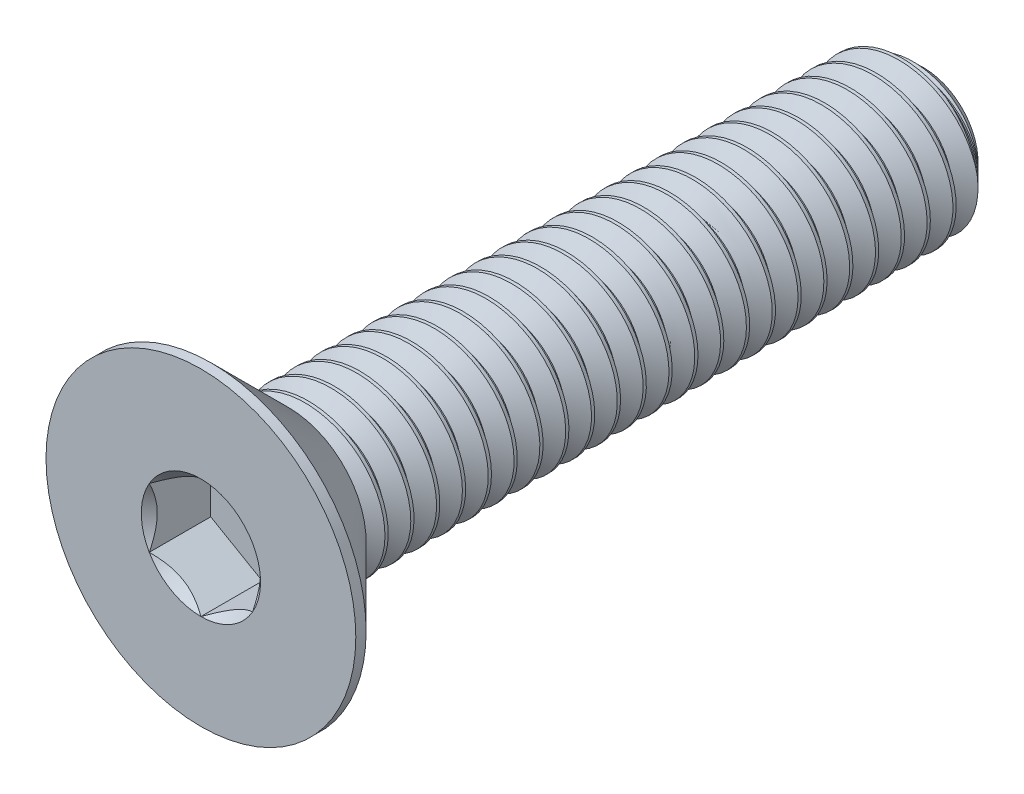
SolidWorks part; units mm, degrees
ref_plane "Front" through (0, 0, 0) normal (0, 0, 1) x (1, 0, 0)
ref_plane "Top" through (0, 0, 0) normal (0, 1, 0) x (1, 0, 0)
ref_plane "Right" through (0, 0, 0) normal (1, 0, 0) x (0, 0, -1)
sketch "Sketch1" plane through (0, 0, 0) normal (1, 0, 0) x (0, 0, -1)
  line L0 (-7, 3) -> (-6.8, 3) construction
  line L1 (-6.8, 3) -> (-5.3, 1.5) construction
  line L2 (-7, 1.5) -> (7, 1.5) construction
  line L3 (7, 1.5) -> (7, 0) construction
  line L4 (7, 0) -> (-7, 0) construction
  line L5 (-7, 0) -> (-7, 3) construction
  line L6 (-7, 3) -> (-7, -3) construction
  line L7 (7, 1.5) -> (7, -1.5) construction
  line L8 (-7, -3) -> (-6.8, -3) construction
  line L9 (-6.8, -3) -> (-5.3, -1.5) construction
  line L11 (-7, 1.5) -> (-7, 0) construction
  line L12 (-5.3, 1.5) -> (-5.3, 0) construction
  line L13 (6.9687, 1.5541) -> (7.2187, 1.1211) construction
  line L14 (7.2187, 1.1211) -> (7.4687, 1.5541) construction
  line L15 (7.4687, 1.5541) -> (6.9687, 1.5541) construction
  line L16 (7.2187, 1.5541) -> (7.2187, 1.5) construction
  line L17 (7.2187, 1.5) -> (7.2187, 1.1752) construction
  line L18 (7.2187, 1.1752) -> (7.2187, 1.1211) construction
  line L19 (7.2187, 1.5271) -> (7.4531, 1.5271) construction
  line L20 (7.2187, 1.5271) -> (6.9844, 1.5271) construction
  line L21 (7, 1.5) -> (7.4375, 1.5) construction
  line L22 (7.1875, 1.1752) -> (7.25, 1.1752) construction
  line L23 (7, -1.5) -> (-5.3, -1.5) construction
  point P10 (5.75, -1.5)
  point P24 (-5.3, 1.5)
  point P30 (0, 0)
  dimension "Head Diameter" = 6
  dimension "Head Height" = 1.7
  dimension "Length" = 14
  dimension "Countersink Angle" = 90
  dimension "Thread Pitch" = 0.5
  dimension "D2" = 0.0625
  dimension "Minimum Thread Length" = 12.3
  dimension "Thread Size" = 3
  dimension "D1" = 1.25
sketch "Sketch2" plane through (0, 0, 0) normal (0, 0, 1) x (1, 0, 0)
  line L1 (0, 1.1547) -> (-1, 0.5774) construction
  line L2 (-1, 0.5774) -> (-1, -0.5774) construction
  line L3 (-1, -0.5774) -> (0, -1.1547) construction
  line L4 (0, -1.1547) -> (1, -0.5774) construction
  line L5 (1, -0.5774) -> (1, 0.5774) construction
  line L6 (1, 0.5774) -> (0, 1.1547) construction
  circle A0 centre (0, 0) radius 1 construction
  dimension "Drive Size" = 2
sketch "Sketch3" plane through (0, 0, 0) normal (1, 0, 0) x (0, 0, -1)
  line L0 (-7, 1.5) -> (7, 1.5)
  line L1 (7, 1.5) -> (7, 0)
  line L2 (7, 0) -> (-7, 0)
  line L3 (-7, 0) -> (-7, 1.5)
revolve "Revolve1" add sketch "Sketch3" angle 360 about L4
chamfer "Chamfer1" distance 0.45 angle 45 1 edges at (0, 1.5, -7)
sketch "Sketch6" plane through (0, 0, 0) normal (1, 0, 0) x (0, 0, -1)
  line L0 (-7, 3) -> (-6.8, 3)
  line L1 (-6.8, 3) -> (-5.3, 1.5)
  line L2 (-5.3, 1.5) -> (-5.3, 0)
  line L3 (-5.3, 0) -> (-7, 0)
  line L4 (-7, 0) -> (-7, 3)
revolve "Revolve2" add sketch "Sketch6" angle 360 about L4
sketch "Sketch8" plane through (0, 0, 7) normal (0, 0, 1) x (1, 0, 0)
  line L0 (0, 1.1547) -> (-1, 0.5774) construction
  line L1 (1, 0.5774) -> (0, 1.1547) construction
  line L2 (1, -0.5774) -> (1, 0.5774) construction
  line L3 (0, -1.1547) -> (1, -0.5774) construction
  line L4 (-1, 0.5774) -> (-1, -0.5774) construction
  line L5 (-1, -0.5774) -> (0, -1.1547) construction
  line L6 (0, 1.1547) -> (-1, 0.5774)
  line L7 (1, 0.5774) -> (0, 1.1547)
  line L8 (1, -0.5774) -> (1, 0.5774)
  line L9 (0, -1.1547) -> (1, -0.5774)
  line L10 (-1, 0.5774) -> (-1, -0.5774)
  line L11 (-1, -0.5774) -> (0, -1.1547)
extrude "Cut-Extrude1" cut sketch "Sketch8" against normal blind 1.19
sketch "Sketch9" plane through (0, 0, 7) normal (0, 0, 1) x (1, 0, 0)
  circle A0 centre (0, 0) radius 1.1547
extrude "Cut-Extrude2" cut sketch "Sketch9" against normal up to next (1.19 mm away) draft 45
ref_plane "Plane1" through (0, 0, 5.3) normal (0, 0, 1) x (1, 0, 0)
split "Split1" trim tools "Plane1" bodies to split 124 resulting bodies 126 127
sketch "Sketch4" plane through (0, 0, -7) normal (0, 0, -1) x (-1, 0, 0)
  circle A0 centre (0, 0) radius 1.5 construction
  circle A1 centre (0, 0) radius 1.5
curve "Helix/Spiral1" pitch 0.5 height 12.8 radius 1.5 centre (0, 0, -7) axis (0, 0, 1) start towards (0, 1, 0)
sketch "Sketch10" plane through (0, 0, 0) normal (1, 0, 0) x (0, 0, -1)
  line L0 (6.9844, 1.5271) -> (7.4531, 1.5271)
  line L1 (7.4531, 1.5271) -> (7.25, 1.1752)
  line L2 (7.25, 1.1752) -> (7.1875, 1.1752)
  line L3 (7.1875, 1.1752) -> (6.9844, 1.5271)
sweep "Cut-Sweep1" cut profiles "Sketch10" path "Helix/Spiral1"
equation "\"D2@Sketch1\" = \"Thread Pitch@Sketch1\" / 8"
equation "\"D4@Helix/Spiral1\"=\"Thread Pitch@Sketch1\""
equation "\"D3@Helix/Spiral1\"=\"Minimum Thread Length@Sketch1\"+\"Thread Pitch@Sketch1\""
equation "\"D1@Chamfer1\"=\"Thread Size@Sketch1\"*.15"
equation "\"D1@Cut-Extrude1\"=\"Head Height@Sketch1\"*.7"
equation "\"D1@Sketch1\"=\"Thread Pitch@Sketch1\"*2.5"
